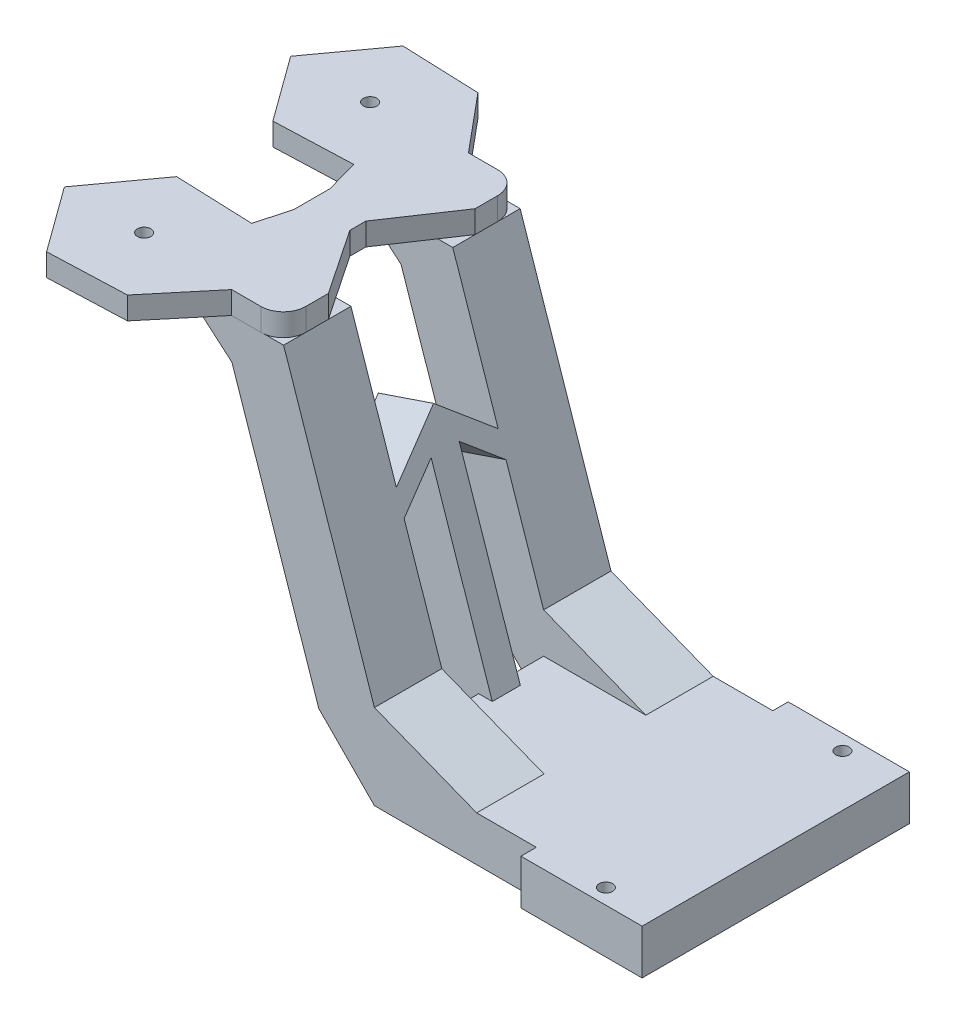
SolidWorks part; units mm, degrees
material "PET"
ref_plane "Alzado" through (0, 0, 0) normal (0, 0, 1) x (1, 0, 0)
ref_plane "Planta" through (0, 0, 0) normal (0, 1, 0) x (1, 0, 0)
ref_plane "Vista lateral" through (0, 0, 0) normal (1, 0, 0) x (0, 0, -1)
sketch "Croquis1" plane through (0, 0, 0) normal (0, 1, 0) x (1, 0, 0)
  line L0 (0, 0) -> (-147.535, 0) construction
  line L2 (-189.1955, 26.3448) -> (-153.15, 26.3448)
  line L6 (-189.1955, 26.3448) -> (-120.672, -29.4672) construction
  line L7 (-189.1955, -20.4319) -> (-117.2917, 25.3344) construction
  line L10 (-153.15, 26.3448) -> (-153.15, 29.7699)
  line L11 (-153.15, 29.7699) -> (-126.1478, 29.7699)
  line L12 (-126.1478, 29.7699) -> (-126.1478, -29.7699)
  line L17 (-153.15, -29.7699) -> (-126.1478, -29.7699)
  line L18 (-153.15, -26.3448) -> (-153.15, -29.7699)
  line L19 (-189.1955, -26.3448) -> (-189.1955, 26.3448)
  line L20 (-189.1955, -26.3448) -> (-153.15, -26.3448)
  circle A1 centre (-137.6312, 26.3448) radius 1.5
  circle A3 centre (-137.6312, -26.3448) radius 1.5
  point P3 (-156.9577, 0.0873)
  point P17 (-126.1478, 0)
  point P22 (-156.9577, -0.0873)
  dimension "D2" = 147.535
extrude "Saliente-Extruir1" add sketch "Croquis1" along normal blind 10
sketch "Croquis3" plane through (0, 0, 26.3448) normal (0, 0, 1) x (1, 0, 0)
  line L0 (-189.1955, 0) -> (-201.6048, 12.5453)
  line L1 (-189.1955, 10) -> (-153.15, 10) construction
  line L2 (-201.6048, 12.5453) -> (-220.9436, 69.6801)
  line L5 (-209.4336, 78.7242) -> (-189.1955, 18.9327)
  line L6 (-189.1955, 18.9327) -> (-166.4279, 10)
  line L7 (-189.1955, 0) -> (-153.15, 0) construction
  line L9 (-189.1955, 0) -> (-166.4279, 0)
  line L12 (-166.4279, 10) -> (-166.4279, 0)
  line L13 (-220.9436, 69.6801) -> (-231.4951, 78.7242)
  line L14 (-231.4951, 78.7242) -> (-209.4336, 78.7242)
extrude "Saliente-Extruir2" add sketch "Croquis3" against normal blind 15
pattern_linear "MatrizL1" count 2 spacing 37.6896 along (0, 0, -1) of "Saliente-Extruir2"
sketch "Croquis8" plane through (-163.9984, -55.5098, 0) normal (0.9472, 0.3206, 0) x (0, 0, -1)
  line L0 (-11.3448, 104.748) -> (-11.3448, 110.153)
  line L2 (-11.3448, 78.5912) -> (-11.3448, 141.7149) construction
  line L5 (-11.3448, 104.748) -> (-3.1233, 111.6576)
  line L6 (-3.1233, 111.6576) -> (-3.1233, 63.6909)
  line L12 (-3.1233, 63.6909) -> (3.1233, 63.6909)
  line L14 (3.1233, 111.6576) -> (3.1233, 63.6909)
  line L15 (11.3448, 104.748) -> (3.1233, 111.6576)
  line L16 (11.3448, 110.153) -> (11.3448, 104.748)
  line L17 (11.3448, 110.153) -> (0, 119.6875)
  line L18 (-11.3448, 110.153) -> (0, 119.6875)
  point P10 (0, 64.6018)
extrude "Saliente-Extruir3" add sketch "Croquis8" against normal blind 13 contours L12 region at (-194.5012, 34.6079, 0)
sketch "Croquis10" plane through (0, 78.7242, 0) normal (0, 1, 0) x (1, 0, 0)
  line L0 (-234.9788, 25.1732) -> (-262.5889, 25.1732) construction
  line L1 (-214.4336, 26.3448) -> (-220.9436, 26.3448)
  line L2 (-228.4622, -0.0289) -> (-317.8829, -0.0289) construction
  line L10 (-248.8536, 39.6598) -> (-231.4951, 39.0015)
  line L11 (-259.3809, 25.1732) -> (-248.8536, 39.6598)
  line L12 (-248.8536, 10.6865) -> (-259.3809, 25.1732)
  line L13 (-231.4951, 11.3448) -> (-248.8536, 10.6865)
  line L15 (-231.4951, 39.0015) -> (-220.9436, 26.3448)
  line L18 (-209.4336, 26.3448) -> (-209.4336, 11.3448) construction
  line L19 (-209.4336, -16.3652) -> (-219.2085, -1.8187)
  line L28 (-229.458, 3.9998) -> (-231.4951, 11.3448)
  line L29 (-229.458, 3.9998) -> (-229.458, -4.0576)
  line L33 (-209.4336, -21.4027) -> (-209.4336, -16.3652)
  line L34 (-209.4336, 21.3448) -> (-209.4336, 16.3074)
  line L35 (-209.4336, 16.3074) -> (-219.2085, 1.7608)
  line L36 (-229.458, -4.0576) -> (-231.4951, -11.4027)
  line L37 (-219.2085, 1.7608) -> (-219.2085, -1.8187)
  line L38 (-231.4951, -39.0594) -> (-220.9436, -26.4027)
  line L39 (-231.4951, -11.4027) -> (-248.8536, -10.7444)
  line L40 (-248.8536, -10.7444) -> (-259.3809, -25.2311)
  line L41 (-259.3809, -25.2311) -> (-248.8536, -39.7177)
  line L42 (-248.8536, -39.7177) -> (-231.4951, -39.0594)
  line L43 (-214.4336, -26.4027) -> (-220.9436, -26.4027)
  arc A0 (-214.4336, 26.3448) -> (-209.4336, 21.3448) centre (-214.4336, 21.3448) cw
  arc A1 (-214.4336, -26.4027) -> (-209.4336, -21.4027) centre (-214.4336, -21.4027) ccw
  point P19 (-219.2085, -0.0289)
  point P21 (-229.458, -0.0289)
  point P27 (-240.975, 40.1454)
  point P31 (-240.975, -40.2032)
  dimension "D1" = 5
extrude "Saliente-Extruir7" add sketch "Croquis10" along normal blind 5
sketch "Croquis11" plane through (0, 83.7242, 0) normal (0, 1, 0) x (1, 0, 0)
  line L0 (-302.4863, 0) -> (-241.6781, 0) construction
  circle A0 centre (-241.6781, 25.1732) radius 1.5
  circle A1 centre (-241.6781, -25.1732) radius 1.5
fillet "Redondeo2" radius 10 1 edges at (-196.7321, 0.6511, 0)
extrude "Cortar-Extruir2" cut sketch "Croquis11" against normal blind 5
equation "\"80.7.00mm\"=65"
